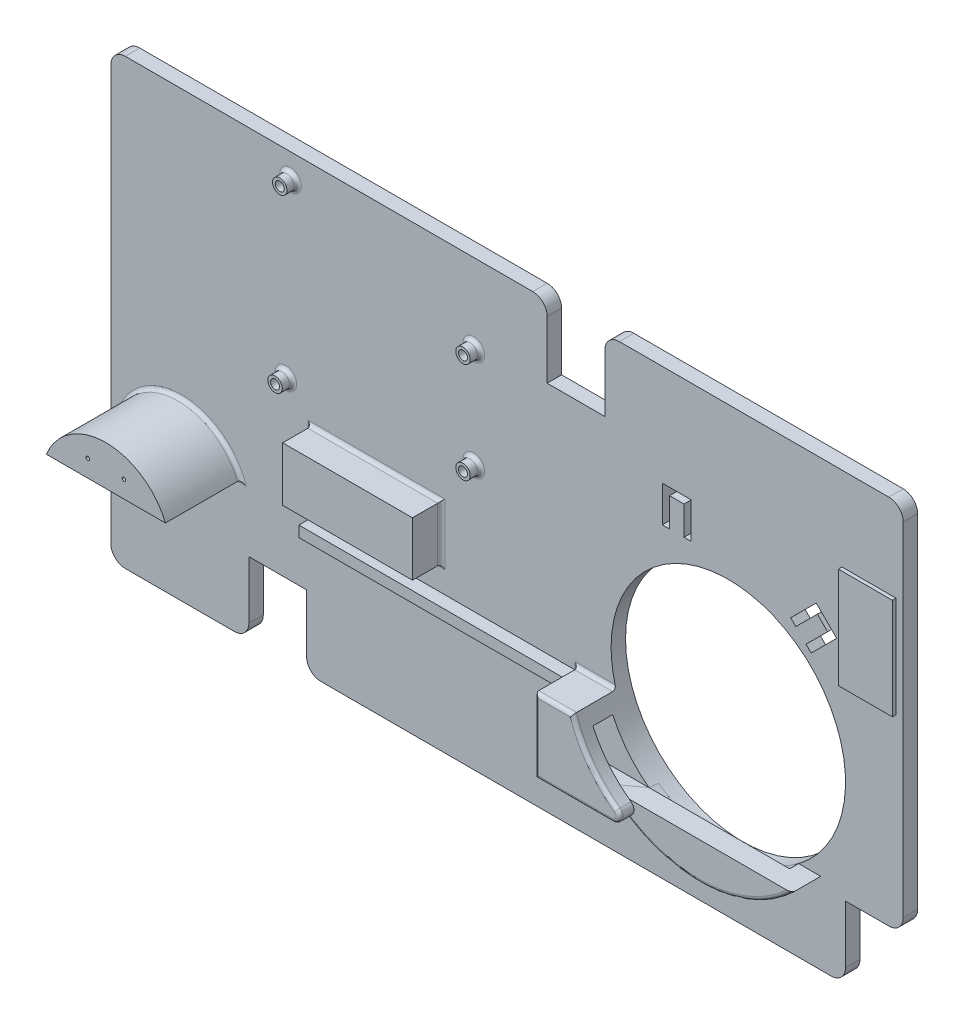
SolidWorks part; units mm, degrees
material "ABS"
ref_plane "Front Plane" through (0, 0, 0) normal (0, 0, 1) x (1, 0, 0)
ref_plane "Top Plane" through (0, 0, 0) normal (0, 1, 0) x (1, 0, 0)
ref_plane "Right Plane" through (0, 0, 0) normal (1, 0, 0) x (0, 0, -1)
sketch "Sketch1" plane through (0, 0, 0) normal (0, 0, 1) x (1, 0, 0)
  line L1 (48.5, 4.5) -> (48.5, -48.5)
  line L2 (48.5, -48.5) -> (-171.1991, -48.5)
  line L3 (-171.1991, -48.5) -> (-171.1991, 74.4853)
  line L4 (-171.1991, 74.4853) -> (48.5, 74.4853)
  line L5 (-10.4575, -32.5) -> (17.6354, -32.5) construction
  line L6 (32.5, 6.3504) -> (32.5, -7.3436) construction
  line L7 (48.5, 74.4853) -> (48.5, 4.5)
  circle A0 centre (0, 0) radius 32.5
  dimension "D1" = 32.5
  dimension "D2" = 16
  dimension "D3" = 53
  dimension "D4" = 16
extrude "Boss-Extrude1" add sketch "Sketch1" along normal blind 4
sketch "Sketch2" plane through (0, 0, 4) normal (0, 0, 1) x (1, 0, 0)
  line L1 (-41.5635, -9.5) -> (-29.5635, -9.5)
  line L2 (-41.5635, -9.5) -> (-41.5635, -13.5)
  line L3 (-41.5635, -13.5) -> (-29.5635, -13.5)
  line L4 (-29.5635, -9.5) -> (-29.5635, -13.5)
  line L5 (-41.5635, -26) -> (-12.5, -26)
  line L6 (-41.5635, -26) -> (-41.5635, -30)
  line L7 (-41.5635, -30) -> (-12.5, -30)
  line L8 (-12.5, -26) -> (-12.5, -30)
  circle A1 centre (0, 0) radius 32.5 construction
  dimension "D1" = 13.5
  dimension "D2" = 12.5
  dimension "D3" = 4
  dimension "D4" = 12
extrude "Boss-Extrude2" add sketch "Sketch2" along normal blind 8
sketch "Sketch3" plane through (0, 0, 12) normal (0, 0, 1) x (1, 0, 0)
  line L1 (-41.5635, -9.5) -> (-12.5, -9.5)
  line L2 (-41.5635, -9.5) -> (-41.5635, -30)
  line L3 (-41.5635, -30) -> (-12.5, -30)
  line L4 (-12.5, -9.5) -> (-12.5, -30)
extrude "Boss-Extrude3" add sketch "Sketch3" along normal blind 4
sketch "Sketch4" plane through (0, 0, 4) normal (0, 0, 1) x (1, 0, 0)
  line L1 (-41.5635, -13.5) -> (-12.5, -13.5)
  line L2 (-41.5635, -13.5) -> (-41.5635, -26)
  line L3 (-41.5635, -26) -> (-12.5, -26)
  line L4 (-12.5, -13.5) -> (-12.5, -26)
extrude "Boss-Extrude4" add sketch "Sketch4" along normal blind 2.5
sketch "Sketch5" plane through (-12.5, 0, 0) normal (1, 0, 0) x (0, 0, -1)
  line L1 (-4, -26) -> (-12, -26)
  line L2 (-4, -26) -> (-4, -36.5)
  line L3 (-4, -36.5) -> (-12, -36.5)
  line L4 (-12, -26) -> (-12, -36.5)
  line L5 (-12, -26) -> (-12, -9.5) construction
  line L6 (-4, -48.5) -> (0, -48.5) construction
  line L7 (-4, -48.5) -> (-4, 74.4853) construction
  dimension "D1" = 12
extrude "Boss-Extrude5" add sketch "Sketch5" along normal blind 40 and the other way blind 20 separate body
sketch "Sketch6" plane through (0, 0, 0) normal (0, 0, -1) x (-1, 0, 0)
  circle A0 centre (0, 0) radius 32.5
  arc A1 (31.0805, -9.5) -> (12.5, -30) centre (0, 0) ccw construction
extrude "Cut-Extrude1" cut sketch "Sketch6" against normal up to surface (6.5 mm away) up to face at (-27.5381, -18.5, 6.5)
sketch "Sketch7" plane through (0, 0, 16) normal (0, 0, 1) x (1, 0, 0)
  circle A0 centre (0, 0) radius 32.5
  arc A1 (-12.5, -30) -> (-31.0805, -9.5) centre (0, 0) ccw construction
extrude "Cut-Extrude2" cut sketch "Sketch7" against normal through all
sketch "Sketch8" plane through (0, 0, 12) normal (0, 0, 1) x (1, 0, 0)
  circle A0 centre (0, 0) radius 36.5
  arc A1 (-12.5, -30) -> (-31.0805, -9.5) centre (0, 0) ccw construction
  dimension "D1" = 4
extrude "Cut-Extrude-Thin1" cut sketch "Sketch8" against normal up to surface (8 mm away) thin up to face at (-61.3495, 12.9926, 4) thin type one direction wall 20
fillet "Fillet1" radius 2 1 edges at (-12.5, -30, 10)
fillet "Fillet2" radius 1 9 edges at (-26.4178, -18.9301, 16) (-18.2522, -28.6138, 16) (-18.2522, -28.6138, 4) (-36.322, -9.5, 4) (-36.322, -9.5, 16) (-30.8596, -30, 16) (-30.8596, -30, 4) (-41.5635, -19.75, 4) (-41.5635, -19.75, 16)
fillet "Fillet3" radius 1 1 edges at (0, -36.5, 12)
sketch "Sketch9" plane through (0, 0, 4) normal (0, 0, 1) x (1, 0, 0)
  line L1 (-141.5635, -3) -> (-161.5635, -3) construction
  line L2 (-141.5635, -3) -> (-141.5635, -11) construction
  line L3 (-141.5635, -11) -> (-161.5635, -11)
  line L4 (-161.5635, -3) -> (-161.5635, -11) construction
  line L5 (-135.0483, -11) -> (-141.5635, -11)
  line L7 (-151.5635, -52.5105) -> (-151.5635, -3) construction
  line L8 (-161.5635, -11) -> (-168.0787, -11)
  line L9 (-29.5635, -13.5) -> (-41.5635, -13.5) construction
  arc A0 (-168.0787, -11) -> (-135.0483, -11) centre (-151.5635, -17.797) cw
  dimension "D1" = 2.5
  dimension "D2" = 100
  dimension "D3" = 20
  dimension "D4" = 8
extrude "Boss-Extrude7" add sketch "Sketch9" along normal blind 21
sketch "Sketch10" plane through (0, 0, 25) normal (0, 0, 1) x (1, 0, 0)
  line L0 (-151.5635, -11) -> (-151.5635, -6.25) construction
  line L2 (-156.5635, -6.25) -> (-146.5635, -6.25) construction
  line L4 (-168.0787, -11) -> (-135.0483, -11) construction
  circle A0 centre (-156.5635, -6.25) radius 0.5
  circle A1 centre (-146.5635, -6.25) radius 0.5
  dimension "D1" = 1
  dimension "D2" = 10
  dimension "D3" = 4.75
extrude "Cut-Extrude3" cut sketch "Sketch10" against normal blind 15
sketch "Sketch11" plane through (0, 0, 4) normal (0, 0, 1) x (1, 0, 0)
  line L0 (-41.5635, -9.5) -> (-41.5635, -30) construction
  line L1 (-79.5635, -3.5) -> (-115.5635, -3.5)
  line L2 (-79.5635, -3.5) -> (-79.5635, 11.5)
  line L3 (-79.5635, 11.5) -> (-115.5635, 11.5)
  line L4 (-115.5635, -3.5) -> (-115.5635, 11.5)
  line L5 (-31.0805, -9.5) -> (-41.5635, -9.5) construction
  dimension "D1" = 38
  dimension "D2" = 6
  dimension "D3" = 36
  dimension "D4" = 15
extrude "Boss-Extrude8" add sketch "Sketch11" along normal blind 8
sketch "Sketch12" plane through (0, 0, 4) normal (0, 0, 1) x (1, 0, 0)
  line L1 (46.5, 23.2256) -> (31.5, 23.2256)
  line L2 (46.5, 23.2256) -> (46.5, 51.2256)
  line L3 (46.5, 51.2256) -> (31.5, 51.2256)
  line L4 (31.5, 23.2256) -> (31.5, 51.2256)
  line L5 (48.5, -48.5) -> (48.5, 74.4853) construction
  dimension "D1" = 28
  dimension "D2" = 15
  dimension "D3" = 2
extrude "Boss-Extrude9" add sketch "Sketch12" along normal blind 1
sketch "Sketch13" plane through (0, 0, 4) normal (0, 0, 1) x (1, 0, 0)
  line L0 (-70.5635, 24.6) -> (-70.5635, 52.5) construction
  line L2 (-79.5635, 11.5) -> (-115.5635, 11.5) construction
  line L3 (-40.5635, -10.5) -> (-40.5635, -29) construction
  circle A0 centre (-122.6635, 19.5) radius 2
  circle A1 centre (-121.3635, 67.7) radius 2
  circle A2 centre (-70.5635, 24.6) radius 2
  circle A3 centre (-70.5635, 52.5) radius 2
  dimension "D6" = 4
  dimension "D1" = 5.1
  dimension "D2" = 27.9
  dimension "D3" = 15.2
  dimension "D4" = 50.8
  dimension "D5" = 1.3
  dimension "D7" = 8
  dimension "D8" = 30
extrude "Boss-Extrude10" add sketch "Sketch13" along normal blind 3
sketch "Sketch15" plane through (0, 0, 7) normal (0, 0, 1) x (1, 0, 0)
  circle A0 centre (-70.5635, 24.6) radius 1.25
  circle A1 centre (-70.5635, 52.5) radius 1.25
  circle A2 centre (-122.6635, 19.5) radius 1.25
  circle A3 centre (-121.3635, 67.7) radius 1.25
  dimension "D1" = 2.5
extrude "Cut-Extrude4" cut sketch "Sketch15" against normal through all
fillet "Fillet4" radius 1 10 edges at (-123.3635, 67.7, 4) (-124.6635, 19.5, 4) (-72.5635, 52.5, 4) (-72.5635, 24.6, 4) (-97.5635, 11.5, 4) (-79.5635, 4, 4) (-151.5635, 0.0622, 4) (-151.5635, -11, 4) (-115.5635, 4, 4) (-97.5635, -3.5, 4)
sketch "Sketch16" plane through (0, 0, 4) normal (0, 0, 1) x (1, 0, 0)
  line L0 (22.9636, 26.2771) -> (30.0347, 33.3482)
  line L1 (30.0347, 33.3482) -> (24.3778, 39.005)
  line L2 (24.3778, 39.005) -> (17.3068, 31.934)
  line L3 (17.3068, 31.934) -> (22.9636, 26.2771) construction
  line L4 (-10.2784, 36.4516) -> (-18.2784, 36.4516) construction
  line L5 (-18.2784, 36.4516) -> (-18.2784, 46.4516)
  line L6 (-18.2784, 46.4516) -> (-10.2784, 46.4516)
  line L7 (-10.2784, 46.4516) -> (-10.2784, 36.4516)
  line L8 (18.721, 30.5198) -> (24.7021, 36.5009)
  line L9 (24.7021, 36.5009) -> (27.5306, 33.6725)
  line L10 (27.5306, 33.6725) -> (21.5494, 27.6913)
  line L11 (22.9636, 26.2771) -> (21.5494, 27.6913)
  line L12 (18.721, 30.5198) -> (17.3068, 31.934)
  line L13 (26.403, 34.8001) -> (27.4929, 35.89) construction
  line L14 (-16.2784, 36.4516) -> (-16.2784, 44.4516)
  line L15 (-16.2784, 44.4516) -> (-12.2784, 44.4516)
  line L16 (-12.2784, 44.4516) -> (-12.2784, 36.4516)
  line L17 (-10.2784, 36.4516) -> (-12.2784, 36.4516)
  line L18 (-12.2784, 36.4516) -> (-12.2313, 36.4409)
  line L19 (-16.2784, 36.4516) -> (-18.2784, 36.4516)
  line L20 (-12.2784, 44.4516) -> (-12.2784, 46.4516) construction
  dimension "D1" = 8
  dimension "D2" = 10
  dimension "D3" = 2
  dimension "D4" = 1.5413
extrude "Cut-Extrude5" cut sketch "Sketch16" against normal through all contours L12 L8 L9 L10 L11 L0 L1 L2 | L16 L15 L14 L19 L5 L6 L7 L17 region at (22.3838, 27.1115, 4)
sketch "Sketch17" plane through (0, 0, 0) normal (0, 0, -1) x (-1, 0, 0)
  line L0 (12.2784, 44.4516) -> (12.2784, 36.4516) construction
  line L1 (16.2784, 36.4516) -> (12.2784, 36.4516)
  line L2 (16.2784, 36.4516) -> (16.2784, 42.4516)
  line L3 (16.2784, 42.4516) -> (12.2784, 42.4516)
  line L4 (12.2784, 36.4516) -> (12.2784, 42.4516)
  line L5 (-18.721, 30.5198) -> (-23.2879, 35.0867)
  line L6 (-18.721, 30.5198) -> (-24.7021, 36.5009) construction
  line L7 (-23.2879, 35.0867) -> (-26.1164, 32.2583)
  line L8 (-27.5306, 33.6725) -> (-21.5494, 27.6913) construction
  line L9 (-26.1164, 32.2583) -> (-21.5494, 27.6913)
  line L10 (-21.5494, 27.6913) -> (-18.721, 30.5198)
  line L11 (-24.7021, 36.5009) -> (-27.5306, 33.6725) construction
  line L12 (16.2784, 44.4516) -> (12.2784, 44.4516) construction
  point P12 (-26.1164, 35.0867)
  point P20 (14.2784, 44.4516)
  dimension "D1" = 2
  dimension "D2" = 2
extrude "Cut-Extrude6" cut sketch "Sketch17" against normal blind 2
fillet "Fillet5" radius 1 4 edges at (-14.2784, 44.4516, 0) (-14.2784, 42.4516, 0) (26.1164, 35.0867, 0) (24.7021, 33.6725, 0)
sketch "Sketch18" plane through (0, 0, 4) normal (0, 0, 1) x (1, 0, 0)
  line L0 (48.5, 74.4853) -> (-171.1991, 74.4853) construction
  line L1 (48.5, -48.5) -> (32.5, -48.5)
  line L2 (48.5, -48.5) -> (48.5, -28.5)
  line L3 (48.5, -28.5) -> (32.5, -28.5)
  line L4 (32.5, -48.5) -> (32.5, -28.5)
  line L7 (-116.93, -38.5) -> (-42.215, -38.5) construction
  line L8 (-42.215, -38.5) -> (32.5, -38.5) construction
  line L9 (-50.215, 74.4853) -> (-34.215, 74.4853)
  line L10 (-50.215, 74.4853) -> (-50.215, 54.4853)
  line L11 (-50.215, 54.4853) -> (-34.215, 54.4853)
  line L12 (-34.215, 74.4853) -> (-34.215, 54.4853)
  line L13 (-171.1991, -48.5) -> (48.5, -48.5) construction
  line L14 (-116.93, -48.5) -> (-132.93, -48.5)
  line L15 (-116.93, -48.5) -> (-116.93, -28.5)
  line L16 (-116.93, -28.5) -> (-132.93, -28.5)
  line L17 (-132.93, -48.5) -> (-132.93, -28.5)
  line L18 (-42.215, -38.5) -> (-42.215, 54.4853) construction
  dimension "D1" = 16
  dimension "D2" = 20
extrude "Cut-Extrude7" cut sketch "Sketch18" against normal through all
fillet "Fillet6" radius 4 9 edges at (48.5, 74.4853, 2) (32.5, -48.5, 2) (48.5, -28.5, 2) (-50.215, 74.4853, 2) (-34.215, 74.4853, 2) (-171.1991, 74.4853, 2) (-132.93, -48.5, 2) (-171.1991, -48.5, 2) (-116.93, -48.5, 2)
sketch "Sketch19" plane through (0, 0, 4) normal (0, 0, 1) x (1, 0, 0)
  line L0 (-115.5635, 11.5) -> (-115.5635, -3.5) construction
  line L1 (-115.5635, -13.5) -> (-40.5635, -13.5)
  line L2 (-115.5635, -13.5) -> (-115.5635, -10.5)
  line L3 (-115.5635, -10.5) -> (-40.5635, -10.5)
  line L4 (-40.5635, -13.5) -> (-40.5635, -10.5)
  line L5 (-31.8119, -10.5) -> (-40.5635, -10.5) construction
extrude "Boss-Extrude11" add sketch "Sketch19" along normal blind 3.5
